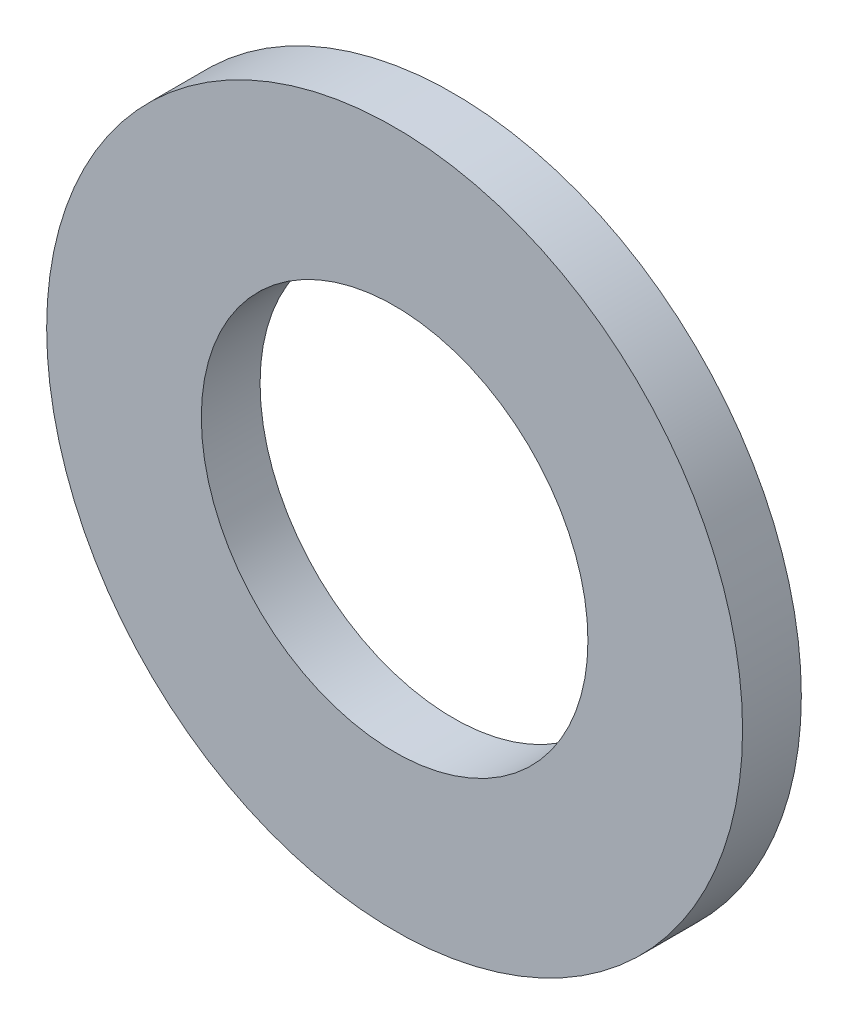
SolidWorks part; units mm, degrees
ref_plane "Front Plane" through (0, 0, 0) normal (0, 0, 1) x (1, 0, 0)
ref_plane "Top Plane" through (0, 0, 0) normal (0, 1, 0) x (1, 0, 0)
ref_plane "Right Plane" through (0, 0, 0) normal (1, 0, 0) x (0, 0, -1)
sketch "Sketch1" plane through (0, 0, 0) normal (0, 0, 1) x (1, 0, 0)
  line L0 (-7.9375, 0) -> (7.9375, 0) construction
  circle A0 centre (0, 0) radius 14.2875 construction
  circle A1 centre (0, 0) radius 7.9375 construction
  dimension "OD" = 28.575
  dimension "ID" = 15.875
  dimension "For Shaft Diameter" = 15.875
sketch "Sketch2" plane through (0, 0, 0) normal (1, 0, 0) x (0, 0, -1)
  line L4 (1.2065, 14.2875) -> (-1.2065, 14.2875) construction
  point P0 (0, 14.2875)
  dimension "Thickness" = 2.413
sketch "Sketch3" plane through (0, 0, 0) normal (0, 0, 1) x (1, 0, 0)
  circle A0 centre (0, 0) radius 7.9375 construction
  circle A1 centre (0, 0) radius 14.2875 construction
  circle A3 centre (0, 0) radius 7.9375
  circle A5 centre (0, 0) radius 14.2875
extrude "Boss-Extrude1" add sketch "Sketch3" against normal up to vertex (-1.2065 mm away) and the other way up to vertex (-1.2065 mm away) up to point (0, 14.2875, 1.2065) other way up to point (0, 14.2875, -1.2065)
equation "\"D1\"= \"Thickness@Sketch2\""
